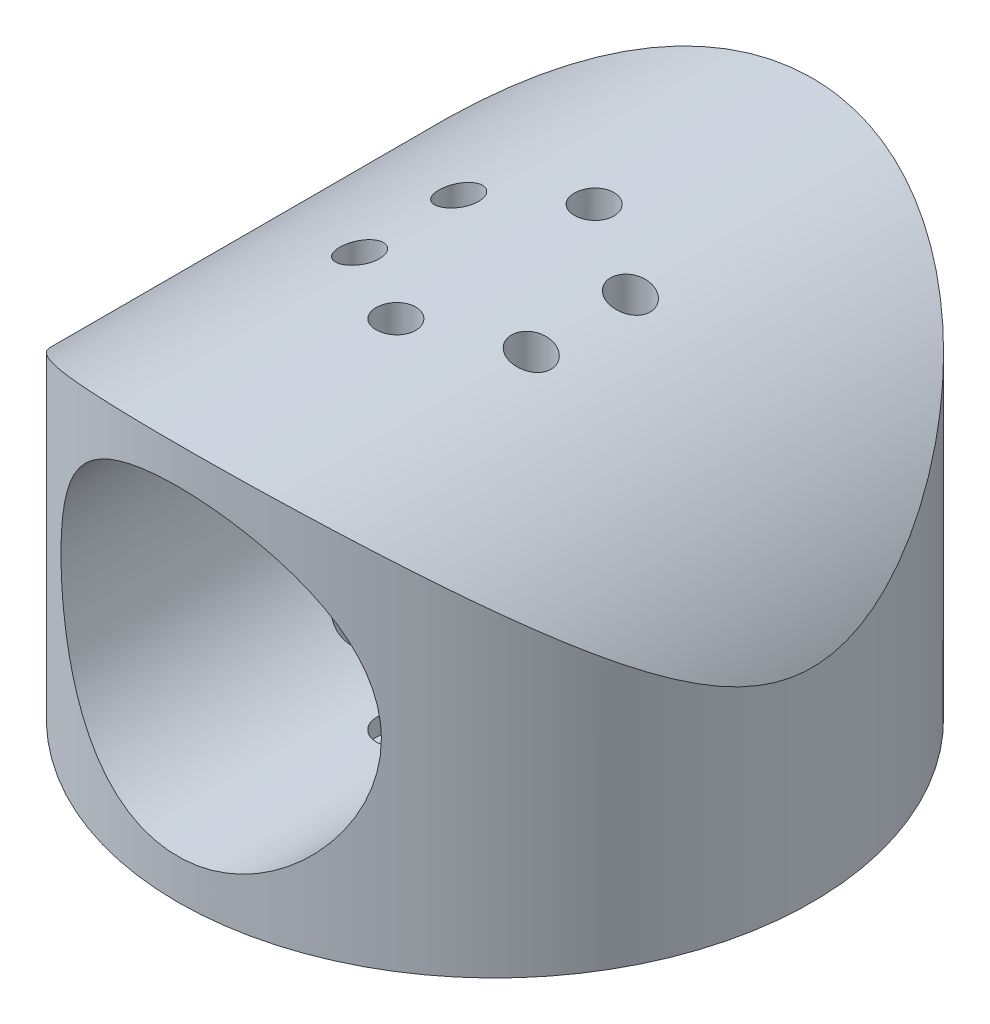
SolidWorks part; units mm, degrees
ref_plane "前视基准面" through (0, 0, 0) normal (0, 0, 1) x (1, 0, 0)
ref_plane "上视基准面" through (0, 0, 0) normal (0, 1, 0) x (1, 0, 0)
ref_plane "右视基准面" through (0, 0, 0) normal (1, 0, 0) x (0, 0, -1)
other "Configuration Table"
sketch "草图1" plane through (0, 0, 0) normal (0, 1, 0) x (1, 0, 0)
  circle A3 centre (0, 0) radius 40
  circle A4 centre (0, 0) radius 45
  dimension "D1" = 90
  dimension "D2" = 80
extrude "凸台-拉伸1" add sketch "草图1" along normal blind 17
sketch "草图4" plane through (0, 0, 0) normal (0, 0, 1) x (1, 0, 0)
  line L0 (0, -1000) -> (0, 49000) construction
  line L4 (-45, 22) -> (-45, 17)
  line L5 (-45, 17) -> (45, 17)
  line L6 (45, 17) -> (45, 22)
  line L7 (-45, 22) -> (45, 22) construction
  circle A0 centre (0, 42.2) radius 20.2
  arc A1 (-45, 22) -> (45, 22) centre (0, 22) cw
  dimension "D1" = 40.4
  dimension "D2" = 5
extrude "凸台-拉伸3" add sketch "草图4" along normal blind 45 and the other way blind 45
sketch "草图5" plane through (0, 17, 0) normal (0, -1, 0) x (1, 0, 0)
  line L1 (-45, -45) -> (45, -45)
  line L2 (-45, -45) -> (-45, 45)
  line L3 (-45, 45) -> (45, 45)
  line L4 (45, -45) -> (45, 45)
  line L5 (-45, -45) -> (45, 45) construction
  line L6 (-45, 45) -> (45, -45) construction
  circle A0 centre (0, 0) radius 45
  circle A1 centre (0, 0) radius 45 construction
  line M1 (-45, 45) -> (-45, 0)
  arc M2 (-45, 0) -> (0, 45) centre (0, 0) cw
  line M3 (0, 45) -> (-45, 45)
extrude "切除-拉伸1" cut sketch "草图5" against normal through all contours M3 M1 M2 | A0 L4 L3 | A0 L1 L4 | A0 L2 L1 region at (-34.9484, 17, -34.9484) region at (34.9484, 17, -34.9484) region at (-34.9484, 17, 34.9484) region at (34.9484, 17, 34.9484)
sketch "草图6" plane through (0, 17, 0) normal (0, -1, 0) x (1, 0, 0)
  line L0 (-1000, 0) -> (49000, 0) construction
  line L1 (-5.1, -8.8335) -> (0, 0) construction
  circle A0 centre (0, 0) radius 10.2 construction
  circle A2 centre (-5.1, -8.8335) radius 1.5
  circle A3 centre (10.2, 0) radius 1.5
  circle A4 centre (-5.1, 8.8335) radius 1.5
  point P3 (0, 0)
  dimension "D1" = 20.4
  dimension "D3" = 3
  dimension "D4" = 3
  dimension "D2" = 60
extrude "切除-拉伸3" cut sketch "草图6" against normal blind 4.8
sketch "草图7" plane through (0, 0, 0) normal (0, -1, 0) x (1, 0, 0)
  circle A0 centre (0, 0) radius 45
extrude "切除-拉伸5" cut sketch "草图7" against normal up to surface (17 mm away) up to face at (-5.1, 17, -10.3335)
sketch "草图8" plane through (0, 17, 0) normal (0, -1, 0) x (1, 0, 0)
  circle A0 centre (0, 0) radius 40
  circle A1 centre (0, 0) radius 45
  dimension "D1" = 80
extrude "切除-拉伸6" cut sketch "草图8" against normal through all
sketch "草图9" plane through (0, 17, 0) normal (0, -1, 0) x (1, 0, 0)
  line L0 (0, -1000) -> (0, 49000) construction
  line L1 (-1000, 0) -> (49000, 0) construction
  line L2 (10.8253, 6.25) -> (0, 0) construction
  circle A0 centre (0, 0) radius 12.5 construction
  circle A1 centre (10.8253, 6.25) radius 1.5
  circle A4 centre (-10.8253, 6.25) radius 1.5
  circle A5 centre (-10.8253, -6.25) radius 1.5
  circle A6 centre (10.8253, -6.25) radius 1.5
  circle A7 centre (0, 12.5) radius 1.5
  circle A8 centre (0, -12.5) radius 1.5
  dimension "D1" = 25
  dimension "D3" = 3
  dimension "D4" = 3
  dimension "D2" = 30
extrude "切除-拉伸7" cut sketch "草图9" against normal through all
ref_plane "基准面1" through (0, 20, 0) normal (0, -1, 0) x (-1, 0, 0)
sketch "草图10" plane through (0, 20, 0) normal (0, -1, 0) x (1, 0, 0)
  line L0 (-1000, 0) -> (49000, 0) construction
  line L1 (-500, -866.0254) -> (24500, 42435.2448) construction
  circle A0 centre (0, 12.5) radius 2.5
  circle A1 centre (10.8253, 6.25) radius 2.5
  circle A2 centre (10.8253, -6.25) radius 2.5
  circle A3 centre (0, -12.5) radius 2.5
  circle A4 centre (-10.8253, 6.25) radius 2.5
  circle A5 centre (-10.8253, -6.25) radius 2.5
  dimension "D2" = 5
  dimension "D1" = 60
extrude "切除-拉伸8" cut sketch "草图10" against normal through all
